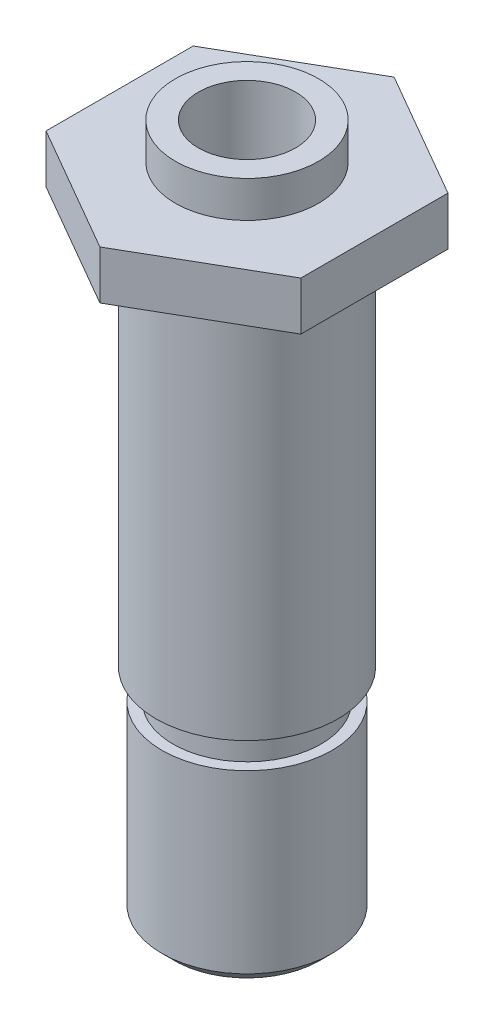
SolidWorks part; units mm, degrees
ref_plane "Спереди" through (0, 0, 0) normal (0, 0, 1) x (1, 0, 0)
ref_plane "Сверху" through (0, 0, 0) normal (0, 1, 0) x (1, 0, 0)
ref_plane "Справа" through (0, 0, 0) normal (1, 0, 0) x (0, 0, -1)
sketch "Эскиз1" plane through (0, 0, 0) normal (0, 1, 0) x (1, 0, 0)
  line L1 (10.5, -6.0622) -> (10.5, 6.0622)
  line L2 (10.5, 6.0622) -> (0, 12.1244)
  line L3 (0, 12.1244) -> (-10.5, 6.0622)
  line L4 (-10.5, 6.0622) -> (-10.5, -6.0622)
  line L5 (-10.5, -6.0622) -> (0, -12.1244)
  line L6 (0, -12.1244) -> (10.5, -6.0622)
  circle A0 centre (0, 0) radius 10.5 construction
  point P1 (0, 0)
extrude "Бобышка-Вытянуть1" add sketch "Эскиз1" along normal blind 4
sketch "Эскиз2" plane through (0, 4, 0) normal (0, 1, 0) x (1, 0, 0)
  circle A0 centre (0, 0) radius 5.9
extrude "Бобышка-Вытянуть2" add sketch "Эскиз2" along normal blind 3
sketch "Эскиз3" plane through (0, 0, 0) normal (0, -1, 0) x (1, 0, 0)
  circle A0 centre (0, 0) radius 7.5
extrude "Бобышка-Вытянуть3" add sketch "Эскиз3" along normal blind 50
sketch "Эскиз4" plane through (0, 7, 0) normal (0, 1, 0) x (1, 0, 0)
  circle A0 centre (0, 0) radius 4
extrude "Вырез-Вытянуть1" cut sketch "Эскиз4" against normal blind 35
sketch "Эскиз6" plane through (0, 0, 0) normal (1, 0, 0) x (0, 0, -1)
  line L0 (7.5, -50) -> (7.5, -32)
  line L1 (7.5, -32) -> (6.1, -32)
  line L2 (6.1, -32) -> (6.1, -34.5)
  line L3 (6.1, -34.5) -> (7, -34.5)
  line L4 (7, -34.5) -> (7, -50)
  line L5 (-7.5, -50) -> (7.5, -50) construction
  line L6 (7, -50) -> (7.5, -50)
  line L7 (0, -50.5265) -> (0, -31.0084) construction
  line L8 (7.5, -50) -> (7.5, 0) construction
  point P2 (0, 0)
  point P9 (8, -32)
revolve "Вырез-Повернуть1" cut sketch "Эскиз6" angle 360 about L7
sketch "Эскиз7" plane through (0, -50, 0) normal (0, -1, 0) x (1, 0, 0)
  circle A0 centre (0, 0) radius 2
extrude "Вырез-Вытянуть2" cut sketch "Эскиз7" against normal through all
chamfer "Фаска1" distance 1 angle 45 1 edges at (0, -50, -7)
